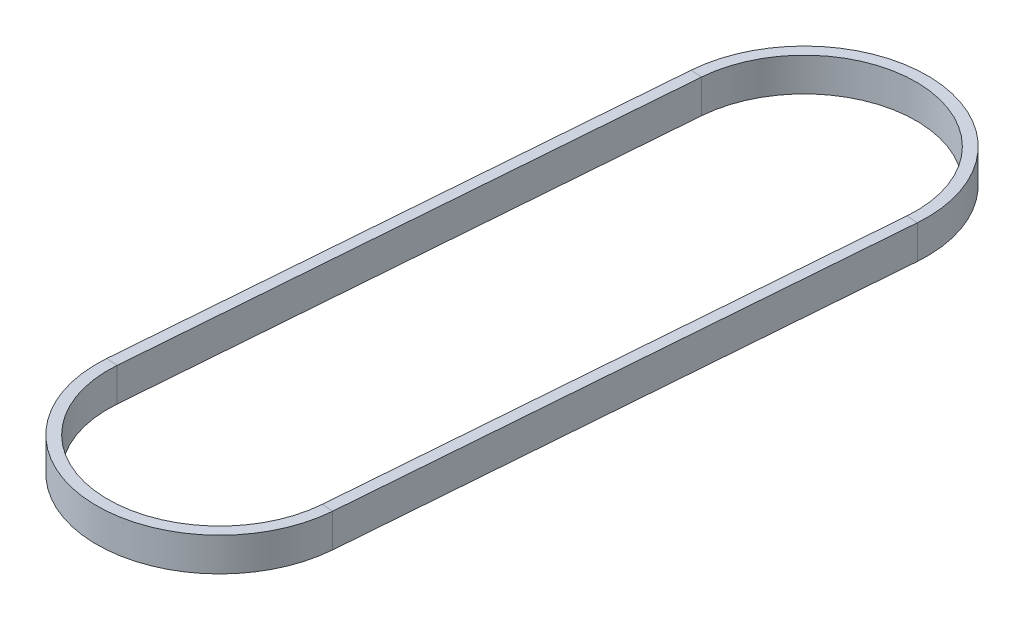
SolidWorks part; units mm, degrees
ref_plane "Front Plane" through (0, 0, 0) normal (0, 0, 1) x (1, 0, 0)
ref_plane "Top Plane" through (0, 0, 0) normal (0, 1, 0) x (1, 0, 0)
ref_plane "Right Plane" through (0, 0, 0) normal (1, 0, 0) x (0, 0, -1)
ref_axis "X" through (-88.99, 0, 0) along (1, 0, 0)
ref_axis "Y" through (0, 0, -88.99) along (0, 0, 1)
ref_axis "Z" through (0, 55, 0) along (0, -1, 0)
sketch "Sketch1" plane through (0, 0, 0) normal (0, 1, 0) x (1, 0, 0)
  line L0 (781.7961, -229.4113) -> (774.1906, -326.3606)
  line L1 (732.3193, -323.0759) -> (739.9248, -226.1266)
  arc A0 (781.7961, -229.4113) -> (739.9248, -226.1266) centre (760.8604, -227.7689) ccw
  arc A1 (732.3193, -323.0759) -> (774.1906, -326.3606) centre (753.255, -324.7182) ccw
  point P4 (753.255, -324.7182)
  point P7 (753.255, -324.7182)
  point P10 (753.255, -324.7182)
  point P16 (760.8604, -227.7689)
  dimension "D1" = 21
  dimension "D2" = 21
ref_plane "Plane1" through (739.9248, 0, 226.1266) normal (0.0782, 0, -0.9969) x (-0.9969, 0, -0.0782)
sketch "Sketch2" plane through (739.9248, 0, 226.1266) normal (0.0782, 0, -0.9969) x (-0.9969, 0, -0.0782)
  line L0 (0, 0) -> (-42, 0) construction
  line L1 (-1, 3) -> (1, 3)
  line L2 (-1, 3) -> (-1, -3)
  line L3 (-1, -3) -> (1, -3)
  line L4 (1, 3) -> (1, -3)
  line L5 (-1, 3) -> (1, -3) construction
  line L6 (-1, -3) -> (1, 3) construction
  point P0 (0, 0)
  dimension "D1" = 2
  dimension "D2" = 6
sweep "Sweep1" add profiles "Sketch2" path "Sketch1"
